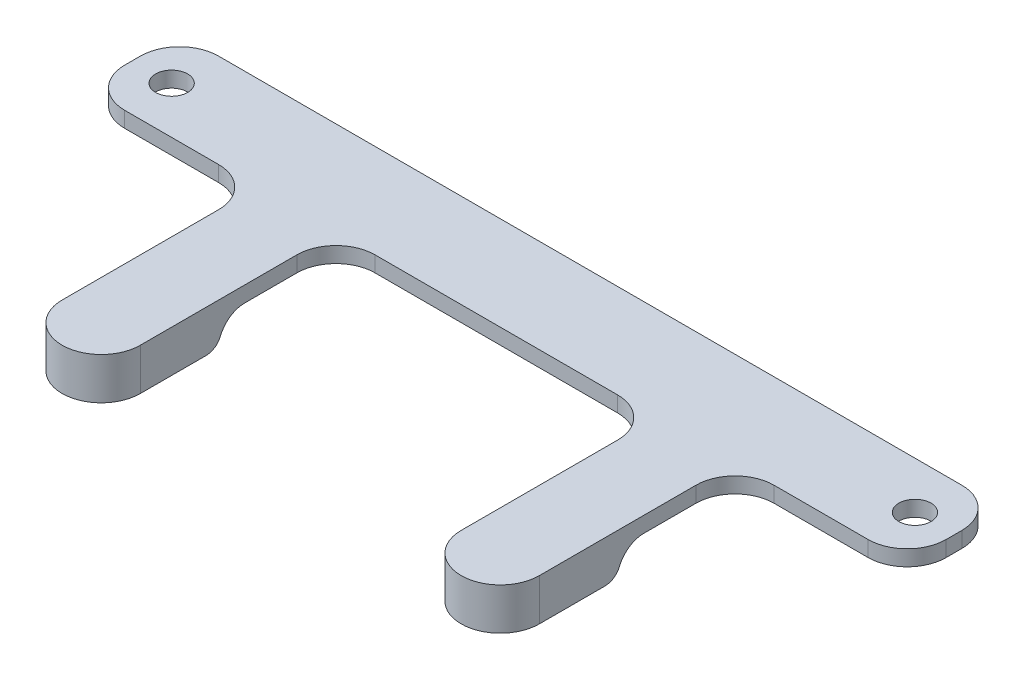
SolidWorks part; units mm, degrees
ref_plane "Front Plane" through (0, 0, 0) normal (0, 0, 1) x (1, 0, 0)
ref_plane "Top Plane" through (0, 0, 0) normal (0, 1, 0) x (1, 0, 0)
ref_plane "Right Plane" through (0, 0, 0) normal (1, 0, 0) x (0, 0, -1)
sketch "Sketch1" plane through (0, 0, 0) normal (0, 1, 0) x (1, 0, 0)
  line L0 (-52.5, 6) -> (52.5, -6) construction
  line L1 (-52.5, 6) -> (52.5, 6)
  line L2 (-52.5, 6) -> (-52.5, -6)
  line L3 (-52.5, -6) -> (-30.5, -6)
  line L4 (52.5, 6) -> (52.5, -6)
  line L7 (-30.5, -6) -> (-30.5, -36)
  line L8 (-30.5, -36) -> (-20.5, -36)
  line L9 (-20.5, -6) -> (-20.5, -36)
  line L10 (0, -55) -> (0, 55) construction
  line L11 (30.5, -36) -> (20.5, -36)
  line L12 (20.5, -6) -> (20.5, -36)
  line L14 (30.5, -6) -> (30.5, -36)
  line L15 (-20.5, -6) -> (20.5, -6)
  line L16 (30.5, -6) -> (52.5, -6)
  dimension "D1" = 105
  dimension "D2" = 12
  dimension "D3" = 10
  dimension "D4" = 22
  dimension "D5" = 30
extrude "Boss-Extrude1" add sketch "Sketch1" along normal blind 2
sketch "Sketch3" plane through (0, 2, 0) normal (0, 1, 0) x (1, 0, 0)
  line L0 (0, -1.1) -> (0, 1.1) construction
  circle A0 centre (-47.5, 0) radius 2.05
  circle A1 centre (47.5, 0) radius 2.05
  dimension "D1" = 4.1
  dimension "D2" = 47.5
extrude "Cut-Extrude1" cut sketch "Sketch3" against normal through all
fillet "Fillet1" radius 5 12 edges at (52.5, 1, -6) (52.5, 1, 6) (20.5, 1, 6) (30.5, 1, 6) (30.5, 1, 36) (20.5, 1, 36) (-30.5, 1, 36) (-20.5, 1, 36) (-20.5, 1, 6) (-30.5, 1, 6) (-52.5, 1, -6) (-52.5, 1, 6)
sketch "Sketch4" plane through (0, 2, 0) normal (0, 1, 0) x (1, 0, 0)
  line L0 (-20.5, -31) -> (-20.5, -11) construction
  line L1 (-30.5, -11) -> (-30.5, -31) construction
  line L2 (-20.5, -31) -> (-20.5, -21)
  line L3 (-30.5, -21) -> (-30.5, -31)
  line L4 (-30.5, -21) -> (-20.5, -21)
  arc A0 (-25.5, -36) -> (-20.5, -31) centre (-25.5, -31) ccw construction
  arc A1 (-30.5, -31) -> (-25.5, -36) centre (-25.5, -31) ccw construction
  arc A2 (-25.5, -36) -> (-20.5, -31) centre (-25.5, -31) ccw
  arc A3 (-30.5, -31) -> (-25.5, -36) centre (-25.5, -31) ccw
extrude "Boss-Extrude2" add sketch "Sketch4" against normal blind 5.35
fillet "Fillet2" radius 3.36 1 edges at (-25.5, 0, 21)
fillet "Fillet3" radius 2 1 edges at (-25.5, -3.35, 21)
mirror "Mirror1" about plane through (0, 0, 0) normal (1, 0, 0) of "Fillet3", "Fillet2", "Boss-Extrude2"
